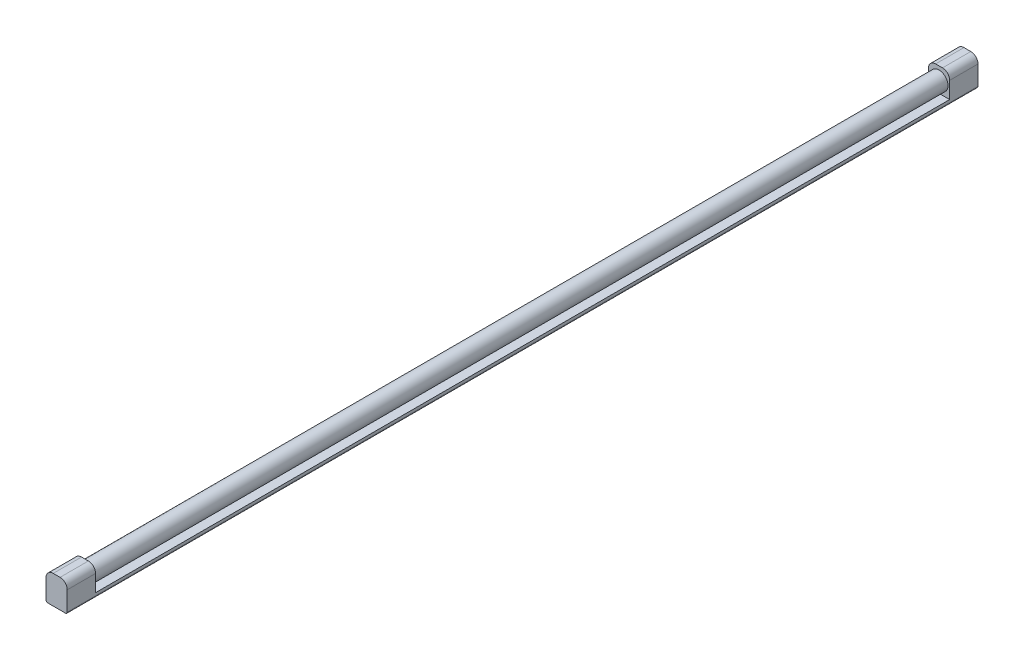
SolidWorks part; units mm, degrees
ref_plane "Front Plane" through (0, 0, 0) normal (0, 0, 1) x (1, 0, 0)
ref_plane "Top Plane" through (0, 0, 0) normal (0, 1, 0) x (1, 0, 0)
ref_plane "Right Plane" through (0, 0, 0) normal (1, 0, 0) x (0, 0, -1)
sketch "Sketch1" plane through (0, 0, 0) normal (0, 0, 1) x (1, 0, 0)
  line L1 (0, 0) -> (30, 0)
  line L2 (0, 0) -> (0, 40)
  line L3 (0, 40) -> (30, 40)
  line L4 (30, 0) -> (30, 40)
  dimension "D1" = 30
  dimension "D2" = 40
extrude "Boss-Extrude1" add sketch "Sketch1" along normal blind 40
fillet "Fillet1" radius 10.16 2 edges at (30, 40, 20) (0, 40, 20)
fillet "Fillet2" radius 2.54 2 edges at (0, 0, 20) (30, 0, 20)
sketch "Sketch3" plane through (0, 0, 40) normal (0, 0, 1) x (1, 0, 0)
  line L0 (15, 40) -> (15, 15.2957) construction
  line L1 (19.84, 40) -> (10.16, 40) construction
  circle A0 centre (15, 22.22) radius 12.7
  dimension "D1" = 25.4
  dimension "D2" = 17.78
extrude "Boss-Extrude2" add sketch "Sketch3" along normal blind 1206
sketch "Sketch6" plane through (0, 0, 1246) normal (0, 0, 1) x (1, 0, 0)
  line L1 (0, 0) -> (30, 0)
  line L2 (0, 0) -> (0, 40)
  line L3 (0, 40) -> (30, 40)
  line L4 (30, 0) -> (30, 40)
extrude "Boss-Extrude3" add sketch "Sketch6" along normal blind 40
fillet "Fillet3" radius 10.16 2 edges at (30, 40, 1266) (0, 40, 1266)
fillet "Fillet4" radius 2.54 2 edges at (0, 0, 1266) (30, 0, 1266)
sketch "Sketch7" plane through (0, 0, 40) normal (0, 0, 1) x (1, 0, 0)
  line L0 (30, 2.54) -> (30, 29.84) construction
  line L1 (0, 0) -> (30, 0)
  line L2 (0, 0) -> (0, 6.35)
  line L3 (0, 6.35) -> (30, 6.35)
  line L4 (30, 0) -> (30, 6.35)
  dimension "D1" = 6.35
extrude "Boss-Extrude4" add sketch "Sketch7" along direction (0, 0, -1) on the side of the normal up to surface (1206 mm away) up to face at (27.7, 22.22, 1246)
fillet "Fillet5" radius 2.54 2 edges at (30, 0, 643) (0, 0, 643)
